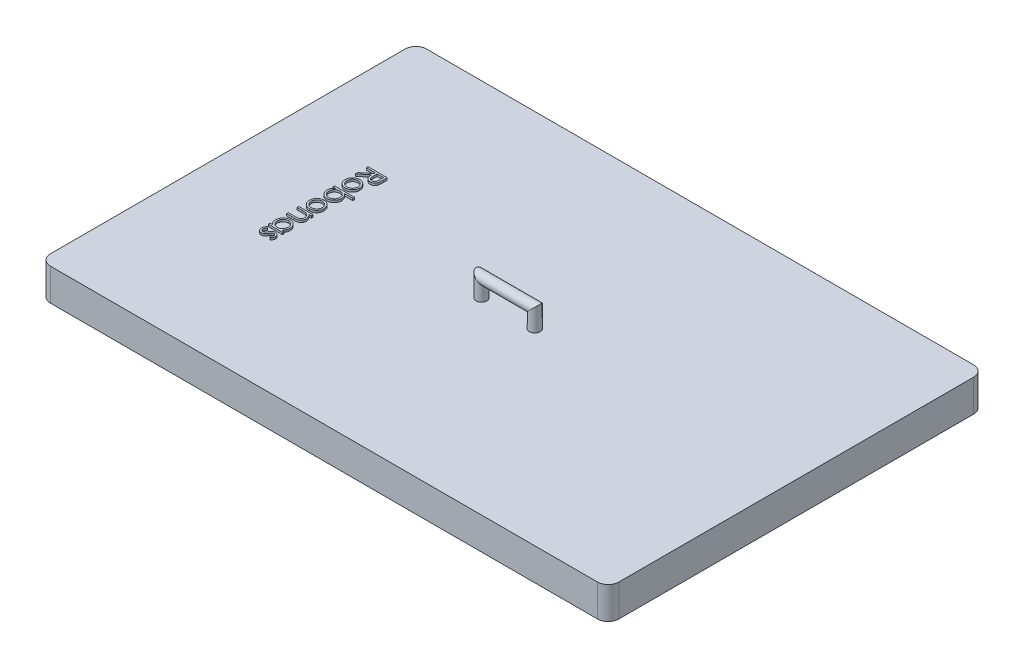
SolidWorks part; units mm, degrees
material "ABS"
ref_plane "Front Plane" through (0, 0, 0) normal (0, 0, 1) x (1, 0, 0)
ref_plane "Top Plane" through (0, 0, 0) normal (0, 1, 0) x (1, 0, 0)
ref_plane "Right Plane" through (0, 0, 0) normal (1, 0, 0) x (0, 0, -1)
sketch "Sketch1" plane through (0, 0, 0) normal (0, 1, 0) x (1, 0, 0)
  line L1 (133, 88) -> (-133, 88)
  line L2 (133, 88) -> (133, -88)
  line L3 (133, -88) -> (-133, -88)
  line L4 (-133, 88) -> (-133, -88)
  line L5 (133, 88) -> (-133, -88) construction
  line L6 (133, -88) -> (-133, 88) construction
  line L7 (-128, -84.6917) -> (128, -84.6917)
  line L8 (-128, -84.6917) -> (-128, 84.6917)
  line L9 (-128, 84.6917) -> (128, 84.6917)
  line L10 (128, -84.6917) -> (128, 84.6917)
  line L11 (-128, -84.6917) -> (128, 84.6917) construction
  line L12 (-128, 84.6917) -> (128, -84.6917) construction
  point P0 (0, 0)
  point P5 (0, 0)
  dimension "D1" = 266
  dimension "D2" = 176
  dimension "D3" = 5
extrude "Boss-Extrude2" add sketch "Sketch1" along normal blind 15 contours L1 L4 L3 L2 L10 L7 L8 L9 | L7 L10 L9 L8 | L8 L7 L10 L9 | L2 L1 L4 L3 region at (129.8105, 0, 0) region at (0, 0, 0)
extrude "Cut-Extrude2" cut sketch "Sketch1<4>" along normal blind 10 contours L7 L10 L9 L8 region at (0, 0, 0)
sketch "Sketch1<4>" plane through (0, 0, 0) normal (0, 1, 0) x (1, 0, 0) same geometry as "Sketch1"
fillet "Fillet1" radius 5 8 edges at (-133, 7.5, -88) (133, 7.5, -88) (-133, 7.5, 88) (133, 7.5, 88) (128, 5, -84.6917) (128, 5, 84.6917) (-128, 5, 84.6917) (-128, 5, -84.6917)
sketch "Sketch2" plane through (0, 0, 0) normal (0, 0, 1) x (1, 0, 0)
  line L0 (-14.2584, 15) -> (-14.2584, 23.6437)
  line L3 (128, 15) -> (-128, 15) construction
  line L4 (-14.2584, 23.6437) -> (10.6676, 23.6437)
  line L5 (10.6676, 23.6437) -> (10.6676, 15)
sketch "Sketch3" plane through (0, 15, 0) normal (0, 1, 0) x (1, 0, 0)
  line L0 (-14.2584, 0) -> (10.6676, 0) construction
  circle A0 centre (10.6676, 0) radius 2.5
  dimension "D1" = 5
sweep "Sweep1" add profiles "Sketch3" path "Sketch2"
sketch "Sketch4" plane through (0, 15, 0) normal (0, 1, 0) x (1, 0, 0)
  line L0 (-93, 88) -> (-93, -88) construction
  line L1 (-133, 83) -> (-133, -83) construction
  line L2 (128, 88) -> (-128, 88) construction
  line L3 (128, -88) -> (-128, -88) construction
  text T0 "Robonas" font "Century Gothic" height 9
  point P2 (-93, 0)
  point P5 (-133, 0)
  dimension "D1" = 40
extrude "Boss-Extrude4" add sketch "Sketch4" along normal blind 1
